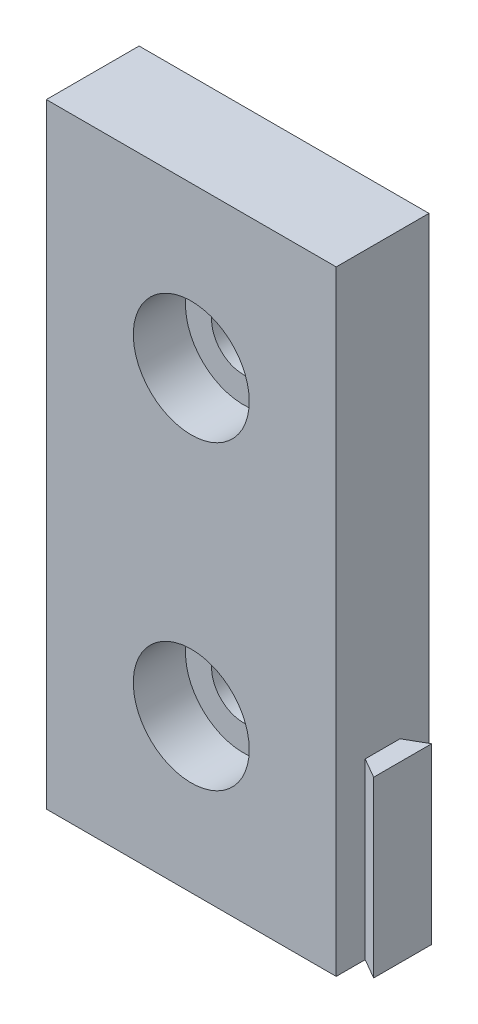
SolidWorks part; units mm, degrees
ref_plane "Front Plane" through (0, 0, 0) normal (0, 0, 1) x (1, 0, 0)
ref_plane "Top Plane" through (0, 0, 0) normal (0, 1, 0) x (1, 0, 0)
ref_plane "Right Plane" through (0, 0, 0) normal (1, 0, 0) x (0, 0, -1)
sketch "Sketch2" plane through (0, 0, 0) normal (0, 0, 1) x (1, 0, 0)
  line L0 (12.5, 53) -> (12.5, -45.5968) construction
  line L1 (0, 0) -> (25, 0)
  line L2 (0, 0) -> (0, 53)
  line L3 (0, 53) -> (25, 53)
  line L4 (25, 0) -> (25, 53)
  line L5 (0, 26.2) -> (42.3407, 26.2) construction
  circle A0 centre (12.5, 39.2) radius 2.75
  circle A1 centre (12.5, 13.2) radius 2.75
  dimension "D3" = 5.5
  dimension "D4" = 13
  dimension "D1" = 53
  dimension "D2" = 25
  dimension "D5" = 13
  dimension "D6" = 26.2
extrude "Boss-Extrude1" add sketch "Sketch2" along normal blind 8
sketch "Sketch3" plane through (0, 0, 0) normal (0, -1, 0) x (1, 0, 0)
  line L0 (25, 2.5) -> (26.7321, 1.5)
  line L1 (26.7321, 1.5) -> (26.7321, 6.5)
  line L2 (26.7321, 6.5) -> (25, 5.5)
  line L3 (25, 8) -> (25, 0) construction
  line L4 (25, 2.5) -> (25, 5.5)
  point P11 (25, 4)
  point P12 (25, 4)
  dimension "D1" = 60
  dimension "D2" = 60
  dimension "D3" = 5
  dimension "D4" = 3
extrude "Boss-Extrude2" add sketch "Sketch3" against normal blind 15
sketch "Sketch4" plane through (0, 0, 8) normal (0, 0, 1) x (1, 0, 0)
  circle A0 centre (12.5, 39.2) radius 5
  circle A1 centre (12.5, 13.2) radius 5
  dimension "D1" = 10
extrude "Cut-Extrude1" cut sketch "Sketch4" against normal blind 4.5
